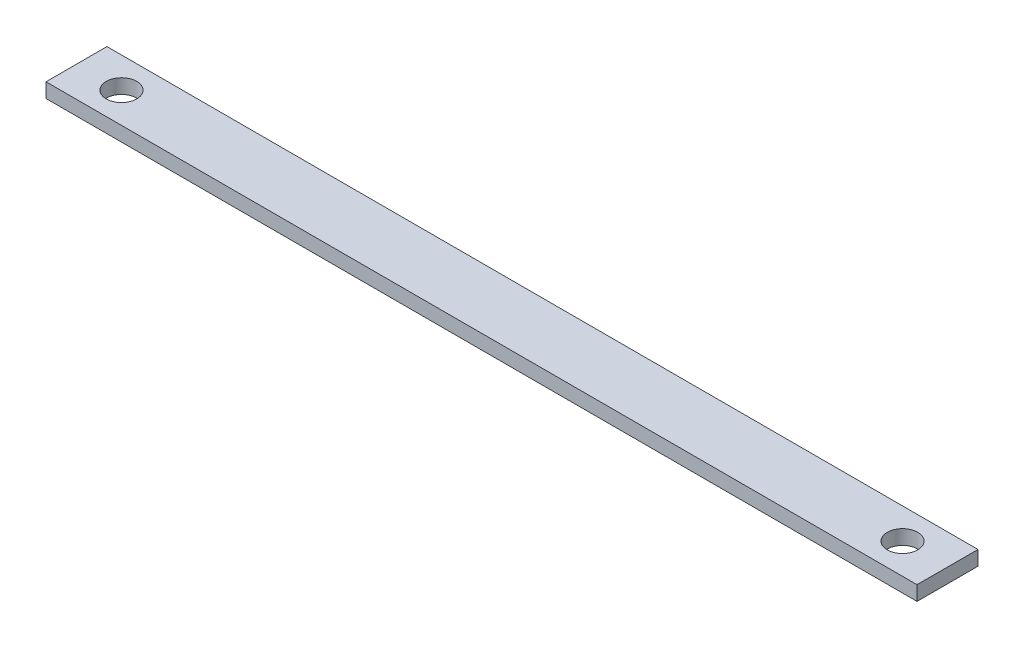
SolidWorks part; units mm, degrees
ref_plane "Plan de face" through (0, 0, 0) normal (0, 0, 1) x (1, 0, 0)
ref_plane "Plan de dessus" through (0, 0, 0) normal (0, 1, 0) x (1, 0, 0)
ref_plane "Plan de droite" through (0, 0, 0) normal (1, 0, 0) x (0, 0, -1)
sketch "Esquisse1" plane through (0, 0, 0) normal (0, 1, 0) x (1, 0, 0)
  line L1 (-300, -21) -> (300, -21)
  line L2 (-300, -21) -> (-300, 21)
  line L3 (-300, 21) -> (300, 21)
  line L4 (300, -21) -> (300, 21)
  line L5 (-300, -21) -> (300, 21) construction
  line L6 (-300, 21) -> (300, -21) construction
  point P0 (0, 0)
  dimension "D1" = 600
  dimension "D2" = 42
extrude "Boss.-Extru.1" add sketch "Esquisse1" along normal blind 10
sketch "Esquisse2" plane through (0, 10, 0) normal (0, 1, 0) x (1, 0, 0)
  line L0 (-238, 21) -> (-238, -21) construction
  line L2 (300, 21) -> (-300, 21) construction
  line L4 (-300, -21) -> (300, -21) construction
  line L5 (-238, 0) -> (-300, 0) construction
  line L6 (-300, 21) -> (-300, -21) construction
  line L8 (238, 21) -> (238, -21) construction
  line L9 (238, 0) -> (300, 0) construction
  line L10 (300, -21) -> (300, 21) construction
  circle A2 centre (269, 0) radius 10.5
  circle A3 centre (-269, 0) radius 10.5
  dimension "D1" = 62
  dimension "D2" = 21
  dimension "D4" = 21
  dimension "D3" = 62
extrude "Enlèv. mat.-Extru.1" cut sketch "Esquisse2" against normal blind 20
